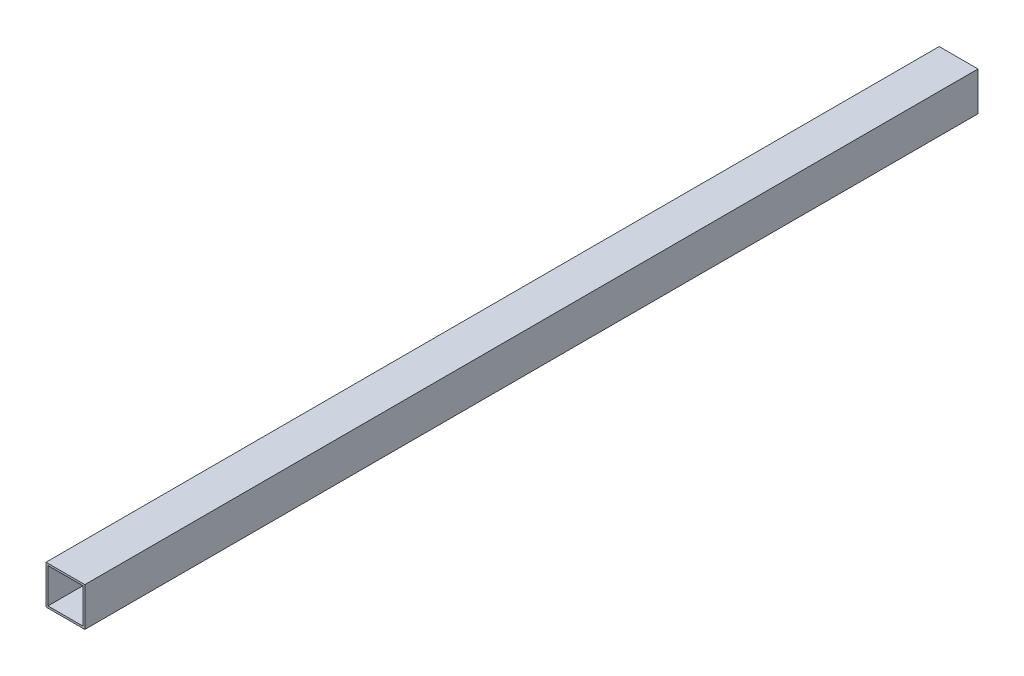
SolidWorks part; units mm, degrees
ref_plane "前视基准面" through (0, 0, 0) normal (0, 0, 1) x (1, 0, 0)
ref_plane "上视基准面" through (0, 0, 0) normal (0, 1, 0) x (1, 0, 0)
ref_plane "右视基准面" through (0, 0, 0) normal (1, 0, 0) x (0, 0, -1)
sketch "草图1" plane through (0, 0, 0) normal (0, 0, 1) x (1, 0, 0)
  line L1 (-10, 10) -> (10, 10)
  line L2 (-10, 10) -> (-10, -10)
  line L3 (-10, -10) -> (10, -10)
  line L4 (10, 10) -> (10, -10)
  line L5 (-10, 10) -> (10, -10) construction
  line L6 (-10, -10) -> (10, 10) construction
  line L7 (-9, 9) -> (9, 9)
  line L8 (-9, 9) -> (-9, -9)
  line L9 (-9, -9) -> (9, -9)
  line L10 (9, 9) -> (9, -9)
  line L11 (-9, 9) -> (9, -9) construction
  line L12 (-9, -9) -> (9, 9) construction
  point P0 (0, 0)
  point P6 (0, 0)
  dimension "D1" = 20
  dimension "D2" = 20
  dimension "D3" = 18
  dimension "D4" = 18
extrude "凸台-拉伸1" add sketch "草图1" along normal blind 460
